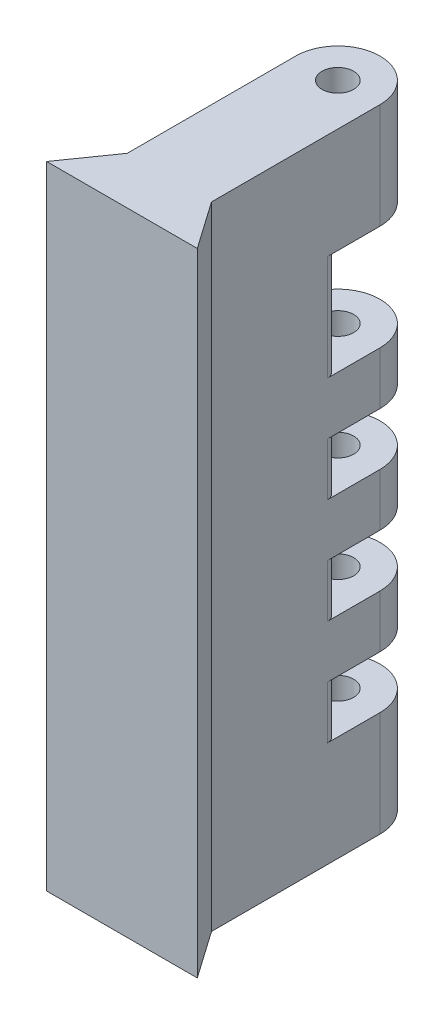
SolidWorks part; units mm, degrees
ref_plane "Front Plane" through (0, 0, 0) normal (0, 0, 1) x (1, 0, 0)
ref_plane "Top Plane" through (0, 0, 0) normal (0, 1, 0) x (1, 0, 0)
ref_plane "Right Plane" through (0, 0, 0) normal (1, 0, 0) x (0, 0, -1)
sketch "Sketch1" plane through (0, 0, 0) normal (0, 1, 0) x (1, 0, 0)
  line L0 (4, 0) -> (-4, 0)
  line L1 (-4, 0) -> (-4, -10)
  line L2 (-4, -10) -> (-4, -14.5) construction
  line L3 (-4, -10) -> (-7.1509, -14.5)
  line L4 (-7.1509, -14.5) -> (-4, -14.5)
  line L5 (0, -7.975) -> (0, 7.975) construction
  line L6 (4, -10) -> (4, -14.5) construction
  line L7 (7.1509, -14.5) -> (4, -14.5)
  line L8 (4, -10) -> (7.1509, -14.5)
  line L9 (4, 0) -> (4, -10)
  line L10 (-4, -14.5) -> (4, -14.5)
  point P12 (0, 0)
  dimension "D1" = 4
  dimension "D2" = 10
  dimension "D3" = 4.5
  dimension "D4" = 145
extrude "Boss-Extrude1" add sketch "Sketch1" along normal blind 60
sketch "Sketch2" plane through (0, 0, 0) normal (0, 1, 0) x (1, 0, 0)
  line L0 (-4, 0) -> (-4, 10)
  line L1 (4, 0) -> (4, 10)
  line L2 (4, 10) -> (-4, 10)
  line L3 (-4, 0) -> (4, 0)
  dimension "D1" = 10
sketch "Sketch3" plane through (0, 0, 0) normal (0, 1, 0) x (1, 0, 0)
  line L0 (0, 10) -> (0, 6) construction
  line L2 (4, 10) -> (-4, 10) construction
  line L3 (0, 6) -> (-4, 6) construction
  line L4 (-4, 0) -> (-4, 10) construction
  line L5 (0, 6) -> (4, 6) construction
  line L6 (4, 0) -> (4, 10) construction
  circle A0 centre (0, 6) radius 2 construction
  circle A1 centre (0, 6) radius 1.5
  dimension "D2" = 4
  dimension "D3" = 3
  dimension "D1" = 4
extrude "Boss-Extrude3" add sketch "Sketch2" along normal blind 60 contours L1 L2 L0 L3
extrude "Cut-Extrude1" cut sketch "Sketch3" along normal blind 60 contours A1
fillet "Fillet1" radius 4 2 edges at (-4, 30, -10) (4, 30, -10)
sketch "Sketch4" plane through (0, 0, 0) normal (1, 0, 0) x (0, 0, -1)
  line L0 (12.6275, 60) -> (16.8881, 60)
  line L1 (16.8881, 60) -> (16.8881, 0)
  line L2 (16.8881, 0) -> (13.4441, 0)
  line L3 (13.4441, 0) -> (13.4441, 10)
  line L4 (13.4441, 10) -> (2, 10)
  line L9 (2, 10) -> (2, 15)
  line L10 (2, 15) -> (13.4441, 15)
  line L11 (13.4441, 15) -> (13.4441, 20)
  line L12 (13.4441, 20) -> (2, 20)
  line L13 (2, 20) -> (2, 25)
  line L14 (2, 25) -> (13.4441, 25)
  line L15 (13.4441, 25) -> (13.4441, 30)
  line L16 (13.4441, 30) -> (2, 30)
  line L17 (2, 30) -> (2, 35)
  line L18 (2, 35) -> (13.4441, 35)
  line L19 (13.4441, 35) -> (13.4441, 40)
  line L20 (13.4441, 40) -> (2, 40)
  line L21 (2, 40) -> (2, 45)
  line L23 (12.6275, 60) -> (12.6275, 50)
  line L24 (12.6275, 50) -> (2, 50)
  line L25 (2, 50) -> (2, 45)
  dimension "D1" = 10
  dimension "D3" = 5
  dimension "D4" = 5
  dimension "D5" = 5
  dimension "D6" = 5
  dimension "D7" = 5
  dimension "D8" = 5
  dimension "D9" = 5
  dimension "D10" = 10
extrude "Cut-Extrude2" cut sketch "Sketch4" against normal blind 60 and the other way blind 60
fillet "Fillet3" radius 1 8 edges at (-4, 12.5, -2) (4, 12.5, -2) (4, 22.5, -2) (-4, 22.5, -2) (-4, 32.5, -2) (4, 32.5, -2) (4, 45, -2) (-4, 45, -2)
